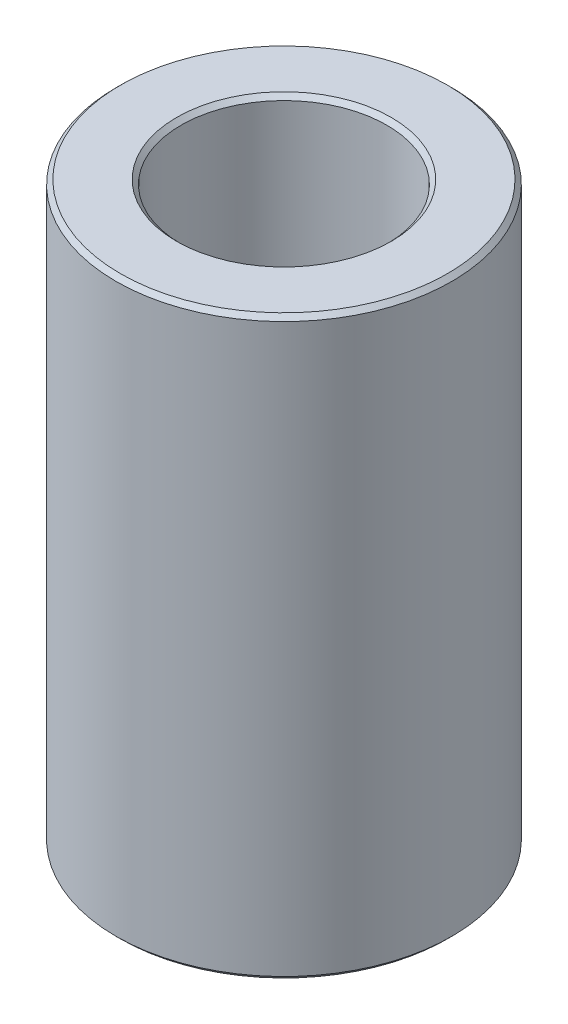
SolidWorks part; units mm, degrees
ref_plane "Front Plane" through (0, 0, 0) normal (0, 0, 1) x (1, 0, 0)
ref_plane "Top Plane" through (0, 0, 0) normal (0, 1, 0) x (1, 0, 0)
ref_plane "Right Plane" through (0, 0, 0) normal (1, 0, 0) x (0, 0, -1)
sketch "Sketch1" plane through (0, 0, 0) normal (0, 1, 0) x (1, 0, 0)
  circle A0 centre (0, 0) radius 42.5
  dimension "SLEEVE_OD" = 85
extrude "Boss-Extrude1" add sketch "Sketch1" along normal blind 145.8538
sketch "Sketch2" plane through (0, 0, 0) normal (0, 1, 0) x (1, 0, 0)
  circle A0 centre (0, 0) radius 26.051
  dimension "BORE_D" = 52.102
extrude "Cut-Extrude1" cut sketch "Sketch2" along normal through all
chamfer "Chamfer1" distance 1.1293 angle 45 4 edges at (0, 145.8538, 26.051) (0, 0, 26.051) (0, 0, 42.5) (0, 145.8538, 42.5)
